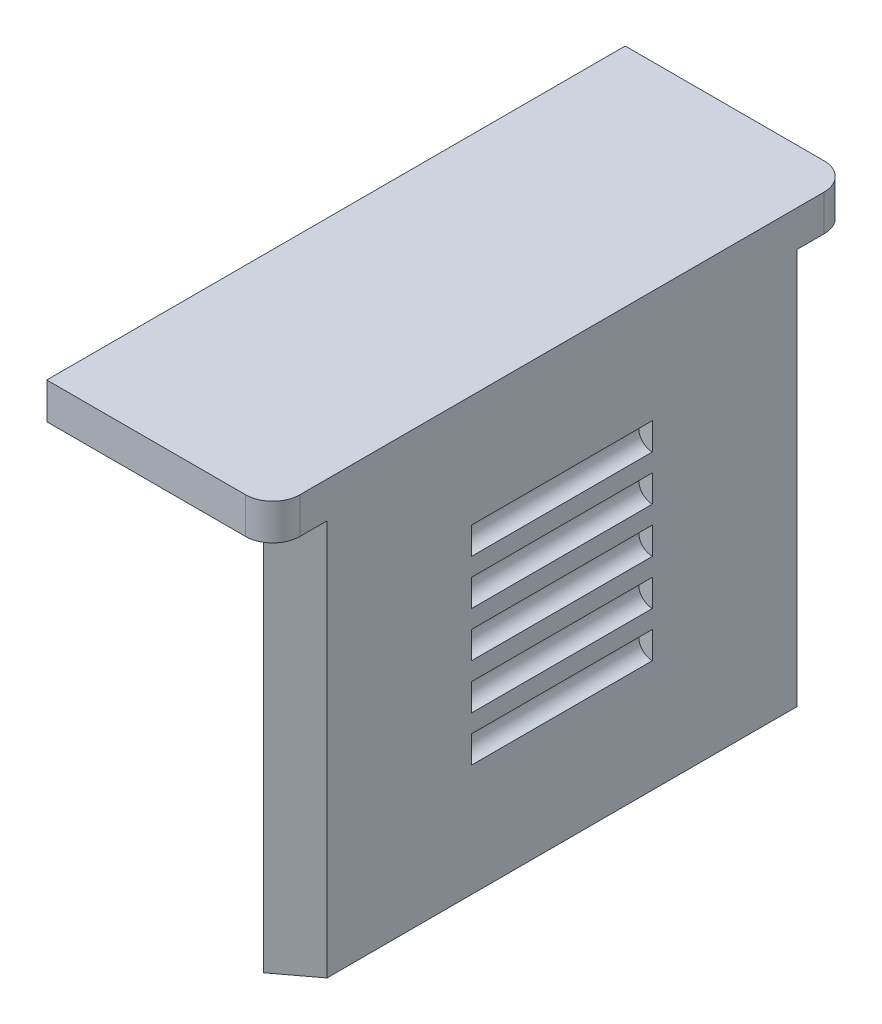
SolidWorks part; units mm, degrees
ref_plane "Alzado" through (0, 0, 0) normal (0, 0, 1) x (1, 0, 0)
ref_plane "Planta" through (0, 0, 0) normal (0, 1, 0) x (1, 0, 0)
ref_plane "Vista lateral" through (0, 0, 0) normal (1, 0, 0) x (0, 0, -1)
sketch "Croquis1" plane through (0, 111.4679, 0) normal (0, 1, 0) x (1, 0, 0)
  line L0 (-3.4522, -72.4184) -> (-15.9522, -72.4184)
  line L5 (-15.9522, -72.4184) -> (-15.9522, -104.4184)
  line L6 (-15.9522, -104.4184) -> (-3.4522, -104.4184)
  line L7 (-3.4522, -104.4184) -> (-3.4522, -72.4184)
  dimension "D1" = 12.5
  dimension "D2" = 32
extrude "Saliente-Extruir1" add sketch "Croquis1" against normal blind 2
sketch "Croquis2" plane through (0, 109.4679, 0) normal (0, -1, 0) x (1, 0, 0)
  line L0 (-3.4522, 101.4184) -> (-5.4522, 102.9184)
  line L3 (-3.4522, 104.4184) -> (-3.4522, 72.4184) construction
  line L4 (-15.9522, 88.4184) -> (1.8923, 88.4184) construction
  line L9 (-5.4522, 102.9184) -> (-5.4522, 73.9184)
  line L10 (-15.9522, 72.4184) -> (-15.9522, 104.4184) construction
  line L12 (-3.4522, 75.4184) -> (-3.4522, 101.4184)
  line L13 (-3.4522, 75.4184) -> (-5.4522, 73.9184)
  dimension "D1" = 2
  dimension "D2" = 2.5
  dimension "D3" = 29
extrude "Saliente-Extruir2" add sketch "Croquis2" along normal blind 21.9
ref_axis "Eje1" through (-3.4522, 111.4679, 88.4184) along (0, -1, 0)
ref_plane "Plano2" through (0, 0, 88.4184) normal (0, 0, 1) x (0, -1, 0)
sketch "Croquis4" plane through (0, 0, 88.4184) normal (0, 0, 1) x (0, -1, 0)
  line L0 (-104.5179, -3.4522) -> (-111.4679, -3.4522) construction
  line L1 (-111.4679, -3.4522) -> (-87.5679, -3.4522) construction
  line L2 (-94.5179, -3.4522) -> (-87.5679, -3.4522) construction
  circle A0 centre (-104.5179, -3.4522) radius 0.75
  circle A1 centre (-102.0179, -3.4522) radius 0.75
  circle A2 centre (-99.5179, -3.4522) radius 0.75
  circle A3 centre (-97.0179, -3.4522) radius 0.75
  circle A4 centre (-94.5179, -3.4522) radius 0.75
  dimension "D2" = 5
  dimension "D3" = 2.5
  dimension "D1" = 1.5
sketch "Croquis5" plane through (0, 109.4679, 0) normal (0, -1, 0) x (1, 0, 0)
  line L0 (-5.4522, 102.9184) -> (-5.4522, 73.9184) construction
  line L1 (-5.4522, 95.9184) -> (-6.4522, 95.9184)
  line L2 (-5.4522, 95.9184) -> (-5.4522, 80.9184)
  line L3 (-5.4522, 80.9184) -> (-6.4522, 80.9184)
  line L4 (-6.4522, 95.9184) -> (-6.4522, 80.9184)
  line L5 (-15.9522, 88.4184) -> (-5.4522, 88.4184) construction
  line L6 (-15.9522, 72.4184) -> (-15.9522, 104.4184) construction
  dimension "D1" = 15
  dimension "D2" = 1
extrude "Saliente-Extruir4" add sketch "Croquis5" along normal blind 20
extrude "Cortar-Extruir1" cut sketch "Croquis4" against normal mid plane 10
fillet "Redondeo1" radius 1.5 2 edges at (-3.4522, 110.4679, 72.4184) (-3.4522, 110.4679, 104.4184)
